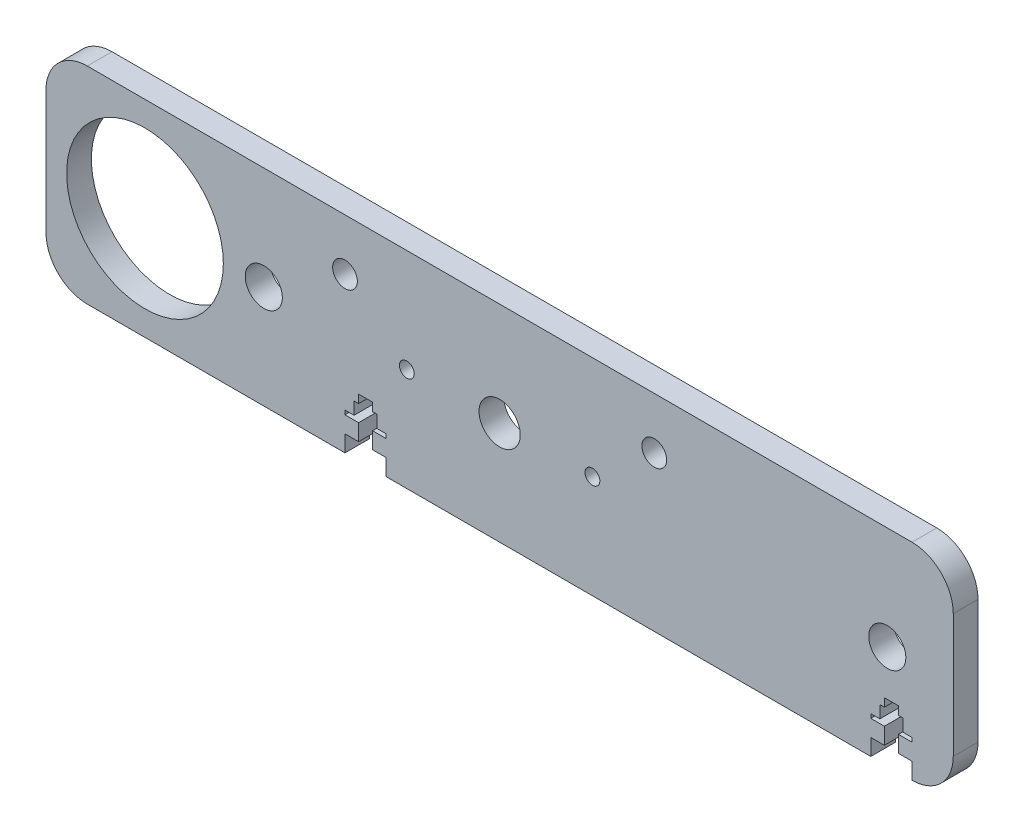
SolidWorks part; units mm, degrees
material "Balsa"
ref_plane "Plano frontal" through (0, 0, 0) normal (0, 0, 1) x (1, 0, 0)
ref_plane "Plano superior" through (0, 0, 0) normal (0, 1, 0) x (1, 0, 0)
ref_plane "Plano direito" through (0, 0, 0) normal (1, 0, 0) x (0, 0, -1)
sketch "Esboço1" plane through (0, 0, 0) normal (0, 0, 1) x (1, 0, 0)
  line L0 (100, -25) -> (100, -21)
  line L1 (-100, -25) -> (-37.5, -25)
  line L2 (-110, -15) -> (-110, 15)
  line L3 (-100, 25) -> (100, 25)
  line L4 (110, -15) -> (110, 15)
  line L5 (-110, -25) -> (110, 25) construction
  line L6 (-110, 25) -> (110, -25) construction
  line L7 (-86, 19) -> (-86, 25) construction
  line L8 (0, 25) -> (0, 0) construction
  line L9 (-52.69, 0) -> (-52.69, 1.5)
  line L10 (-37.5, 12.5) -> (37.5, 12.5) construction
  line L11 (-22.5, 0) -> (22.5, 0) construction
  line L12 (100, -21) -> (96.7, -21)
  line L13 (90, -21) -> (90, -25)
  line L14 (-37.5, -25) -> (-37.5, -21)
  line L15 (-37.5, -21) -> (-34.2, -21)
  line L16 (-27.5, -21) -> (-27.5, -25)
  line L17 (-27.5, -25) -> (90, -25)
  line L18 (-32.5, -25) -> (-32.5, -13.0244) construction
  line L19 (-34.2, -21) -> (-34.2, -17)
  line L20 (-34.2, -17) -> (-37.5, -17)
  line L21 (-35.3, -16) -> (-35.3, -13)
  line L22 (-35.3, -13) -> (-34.2, -13)
  line L23 (-37.5, -25) -> (-27.5, -25) construction
  line L24 (-34.2, -13) -> (-34.2, -11)
  line L25 (-34.2, -11) -> (-30.8, -11)
  line L26 (-35.3, -16) -> (-37.5, -16)
  line L27 (-37.5, -16) -> (-37.5, -17)
  line L28 (-27.5, -16) -> (-27.5, -17)
  line L29 (-29.7, -16) -> (-27.5, -16)
  line L30 (-30.8, -13) -> (-30.8, -11)
  line L31 (-29.7, -13) -> (-30.8, -13)
  line L32 (-29.7, -16) -> (-29.7, -13)
  line L33 (-30.8, -17) -> (-27.5, -17)
  line L34 (-30.8, -21) -> (-30.8, -17)
  line L35 (-27.5, -21) -> (-30.8, -21)
  line L36 (100, -16) -> (100, -17)
  line L37 (90, -16) -> (90, -17)
  line L38 (96.7, -17) -> (100, -17)
  line L39 (93.3, -17) -> (90, -17)
  line L40 (96.7, -13) -> (96.7, -11)
  line L41 (97.8, -13) -> (96.7, -13)
  line L42 (93.3, -13) -> (93.3, -11)
  line L43 (93.3, -11) -> (96.7, -11)
  line L44 (93.3, -21) -> (93.3, -17)
  line L45 (95, -25) -> (95, -15.5244) construction
  line L46 (92.2, -16) -> (92.2, -13)
  line L47 (96.7, -21) -> (96.7, -17)
  line L48 (97.8, -16) -> (100, -16)
  line L49 (92.2, -16) -> (90, -16)
  line L50 (92.2, -13) -> (93.3, -13)
  line L51 (97.8, -16) -> (97.8, -13)
  line L52 (93.3, -21) -> (90, -21)
  circle A0 centre (-86, 0) radius 19
  circle A1 centre (94, 0) radius 4.5
  arc A2 (100, -25) -> (110, -15) centre (100, -15) ccw
  arc A3 (100, 25) -> (110, 15) centre (100, 15) cw
  arc A4 (-110, 15) -> (-100, 25) centre (-100, 15) cw
  arc A5 (-100, -25) -> (-110, -15) centre (-100, -15) cw
  circle A6 centre (0, 0) radius 5
  circle A7 centre (-57.19, 0) radius 4.5
  circle A8 centre (-22.5, 0) radius 1.8
  circle A9 centre (22.5, 0) radius 1.8
  circle A10 centre (-37.5, 12.5) radius 3
  circle A11 centre (37.5, 12.5) radius 3
  point P0 (0, 0)
  point P34 (0, 12.5)
  point P35 (0, 12.5)
  point P42 (0, 0)
  point P60 (-32.5, -25)
  point P67 (-32.5, -11)
  point P84 (94.8463, -8.5)
  dimension "D3" = 38
  dimension "D5" = 9
  dimension "D6" = 10
  dimension "D9" = 28.81
  dimension "D10" = 75
  dimension "D11" = 6
  dimension "D12" = 3.6
  dimension "D14" = 10
  dimension "D1" = 220
  dimension "D2" = 50
  dimension "D4" = 180
  dimension "D7" = 4
  dimension "D8" = 10
  dimension "D13" = 45
  dimension "D15" = 10
  dimension "D16" = 10
  dimension "D17" = 4
  dimension "D18" = 4
  dimension "D19" = 4
  dimension "D20" = 5.6
  dimension "D21" = 3.4
  dimension "D22" = 2
  dimension "D23" = 1
  dimension "D24" = 10
  dimension "D25" = 4
  dimension "D26" = 3.4
  dimension "D27" = 5.6
  dimension "D28" = 2
  dimension "D29" = 4
  dimension "D30" = 1
  dimension "D31" = 10
extrude "Ressalto-extrusão1" add sketch "Esboço1" along normal blind 6 contours A5 L1 A2 L4 A3 L3 A4 L2 A11 A10 A9 A8 A6 A1 A0 A7 region at (9.6259, 0.2821, 0)
